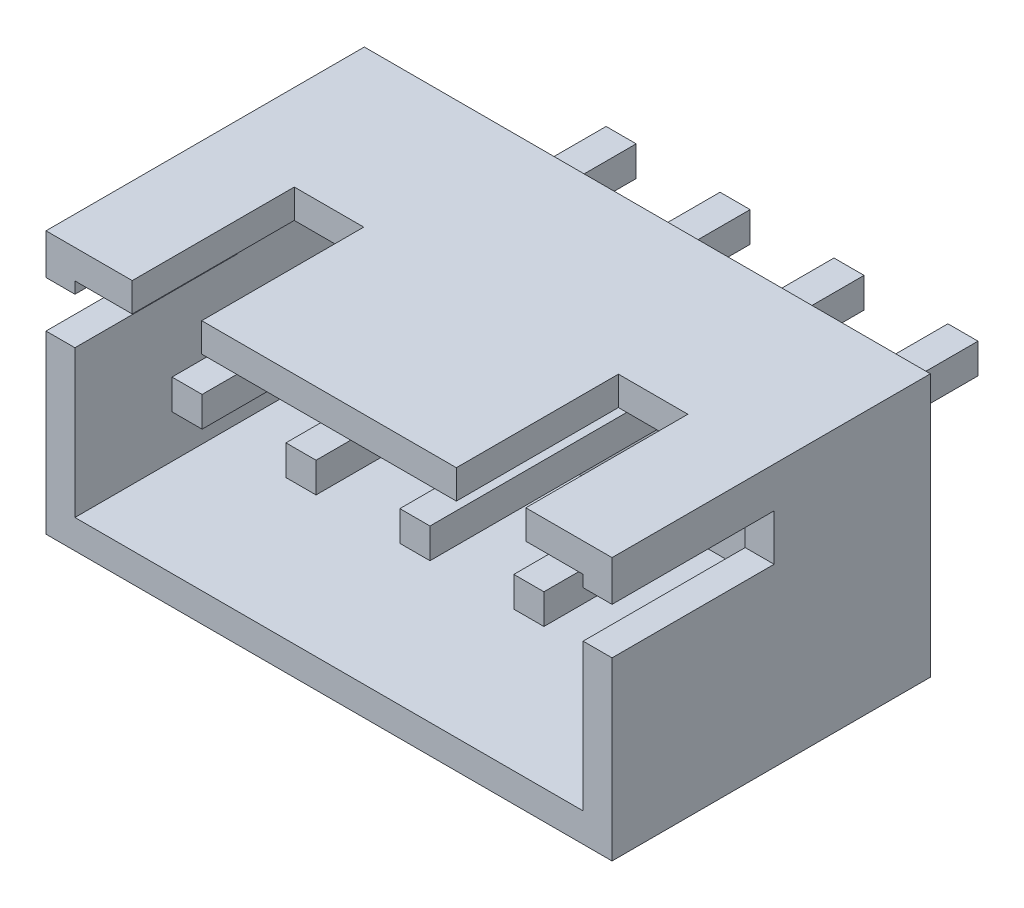
SolidWorks part; units mm, degrees
ref_plane "Front Plane" through (0, 0, 0) normal (0, 0, 1) x (1, 0, 0)
ref_plane "Top Plane" through (0, 0, 0) normal (0, 1, 0) x (1, 0, 0)
ref_plane "Right Plane" through (0, 0, 0) normal (1, 0, 0) x (0, 0, -1)
sketch "Sketch1" plane through (0, 0, 0) normal (0, 0, 1) x (1, 0, 0)
  line L1 (0, 0) -> (12.4206, 0)
  line L2 (0, 0) -> (0, 5.7658)
  line L3 (0, 5.7658) -> (12.4206, 5.7658)
  line L4 (12.4206, 0) -> (12.4206, 5.7658)
  dimension "D1" = 5.7658
  dimension "D2" = 12.4206
extrude "Boss-Extrude1" add sketch "Sketch1" along normal blind 6.985
sketch "Sketch2" plane through (0, 0, 0) normal (0, 0, -1) x (-1, 0, 0)
  line L0 (-9.9603, 3.4036) -> (-7.4603, 3.4036) construction
  line L1 (-7.4603, 3.4036) -> (-4.9603, 3.4036) construction
  line L2 (-7.4603, 3.4036) -> (-7.4603, 5.7658) construction
  line L3 (-12.4206, 5.7658) -> (0, 5.7658) construction
  line L4 (-6.2103, 5.7658) -> (-6.2103, 0) construction
  line L5 (-10.2905, 3.0734) -> (-9.6301, 3.0734)
  line L6 (-10.2905, 3.0734) -> (-10.2905, 3.7338)
  line L7 (-10.2905, 3.7338) -> (-9.6301, 3.7338)
  line L8 (-9.6301, 3.0734) -> (-9.6301, 3.7338)
  line L9 (-10.2905, 3.0734) -> (-9.6301, 3.7338) construction
  line L10 (-10.2905, 3.7338) -> (-9.6301, 3.0734) construction
  line L11 (-7.1301, 3.0734) -> (-7.7905, 3.0734)
  line L12 (-7.1301, 3.0734) -> (-7.1301, 3.7338)
  line L13 (-7.1301, 3.7338) -> (-7.7905, 3.7338)
  line L14 (-7.7905, 3.0734) -> (-7.7905, 3.7338)
  line L15 (-7.1301, 3.0734) -> (-7.7905, 3.7338) construction
  line L16 (-7.1301, 3.7338) -> (-7.7905, 3.0734) construction
  line L17 (-4.6301, 3.0734) -> (-5.2905, 3.0734)
  line L18 (-4.6301, 3.0734) -> (-4.6301, 3.7338)
  line L19 (-4.6301, 3.7338) -> (-5.2905, 3.7338)
  line L20 (-5.2905, 3.0734) -> (-5.2905, 3.7338)
  line L21 (-4.6301, 3.0734) -> (-5.2905, 3.7338) construction
  line L22 (-4.6301, 3.7338) -> (-5.2905, 3.0734) construction
  line L23 (0, 0) -> (-12.4206, 0) construction
  line L24 (-4.9603, 3.4036) -> (-2.4603, 3.4036) construction
  line L26 (-2.7905, 3.0734) -> (-2.1301, 3.0734)
  line L27 (-2.7905, 3.0734) -> (-2.7905, 3.7338)
  line L28 (-2.7905, 3.7338) -> (-2.1301, 3.7338)
  line L29 (-2.1301, 3.0734) -> (-2.1301, 3.7338)
  line L30 (-2.7905, 3.0734) -> (-2.1301, 3.7338) construction
  line L31 (-2.7905, 3.7338) -> (-2.1301, 3.0734) construction
  circle A0 centre (-7.4603, 3.4036) radius 0.3302 construction
  circle A1 centre (-4.9603, 3.4036) radius 0.3302 construction
  circle A2 centre (-9.9603, 3.4036) radius 0.3302 construction
  point P30 (-7.5223, 5.6512)
  point P31 (0, 0)
  point P32 (-7.4603, 5.7658)
  dimension "D1" = 0.6604
  dimension "D2" = 2.5
  dimension "D3" = 2.6924
extrude "Boss-Extrude2" add sketch "Sketch2" along normal blind 3.175
sketch "Sketch4" plane through (0, 0, 6.985) normal (0, 0, 1) x (1, 0, 0)
  line L0 (12.4206, 0) -> (12.4206, 5.7658) construction
  line L1 (0.635, 5.1308) -> (11.7856, 5.1308)
  line L2 (0.635, 5.1308) -> (0.635, 0.635)
  line L3 (0.635, 0.635) -> (11.7856, 0.635)
  line L4 (11.7856, 5.1308) -> (11.7856, 0.635)
  line L5 (0, 0) -> (12.4206, 0) construction
  line L6 (0, 5.7658) -> (0, 0) construction
  line L7 (12.4206, 5.7658) -> (0, 5.7658) construction
  dimension "D1" = 0.635
  dimension "D2" = 0.635
  dimension "D3" = 0.635
  dimension "D4" = 0.635
extrude "Cut-Extrude1" cut sketch "Sketch4" against normal offset from surface (6.35 mm away) 0.635 up to face at (6.2103, 2.8829, 0)
extrude "Boss-Extrude3" add sketch "Sketch2<2>" against normal offset from surface (6.35 mm away) 0.635 up to face at (6.2103, 2.8829, 6.985)
sketch "Sketch2<2>" plane through (0, 0, 0) normal (0, 0, -1) x (-1, 0, 0) same geometry as "Sketch2"
sketch "Sketch5" plane through (0, 0, 6.985) normal (0, 0, 1) x (1, 0, 0)
  line L0 (0, 5.7658) -> (0, 0) construction
  line L1 (0, 4.8768) -> (0.635, 4.8768)
  line L2 (0, 4.8768) -> (0, 3.8608)
  line L3 (0, 3.8608) -> (0.635, 3.8608)
  line L4 (0.635, 4.8768) -> (0.635, 3.8608)
  line L5 (0.635, 5.1308) -> (0.635, 0.635) construction
  line L6 (11.7856, 0.635) -> (11.7856, 5.1308) construction
  line L7 (11.7856, 4.8768) -> (12.4206, 4.8768)
  line L8 (11.7856, 4.8768) -> (11.7856, 3.8608)
  line L9 (11.7856, 3.8608) -> (12.4206, 3.8608)
  line L10 (12.4206, 4.8768) -> (12.4206, 3.8608)
  line L11 (12.4206, 0) -> (12.4206, 5.7658) construction
  line L12 (12.4206, 5.7658) -> (0, 5.7658) construction
  line L13 (9.0043, 5.7658) -> (10.5283, 5.7658)
  line L14 (9.0043, 5.7658) -> (9.0043, 5.1308)
  line L15 (9.0043, 5.1308) -> (10.5283, 5.1308)
  line L16 (10.5283, 5.7658) -> (10.5283, 5.1308)
  line L17 (11.7856, 5.1308) -> (0.635, 5.1308) construction
  line L18 (11.7856, 5.1308) -> (0.635, 5.1308) construction
  line L19 (1.8923, 5.7658) -> (3.4163, 5.7658)
  line L20 (1.8923, 5.7658) -> (1.8923, 5.1308)
  line L21 (1.8923, 5.1308) -> (3.4163, 5.1308)
  line L22 (3.4163, 5.7658) -> (3.4163, 5.1308)
  line L23 (3.4163, 5.4483) -> (9.0043, 5.4483) construction
  line L24 (6.2103, 5.4483) -> (6.2103, 5.7658) construction
  dimension "D1" = 1.016
  dimension "D2" = 0.254
  dimension "D3" = 5.588
  dimension "D4" = 1.524
extrude "Cut-Extrude2" cut sketch "Sketch5" against normal blind 3.556
